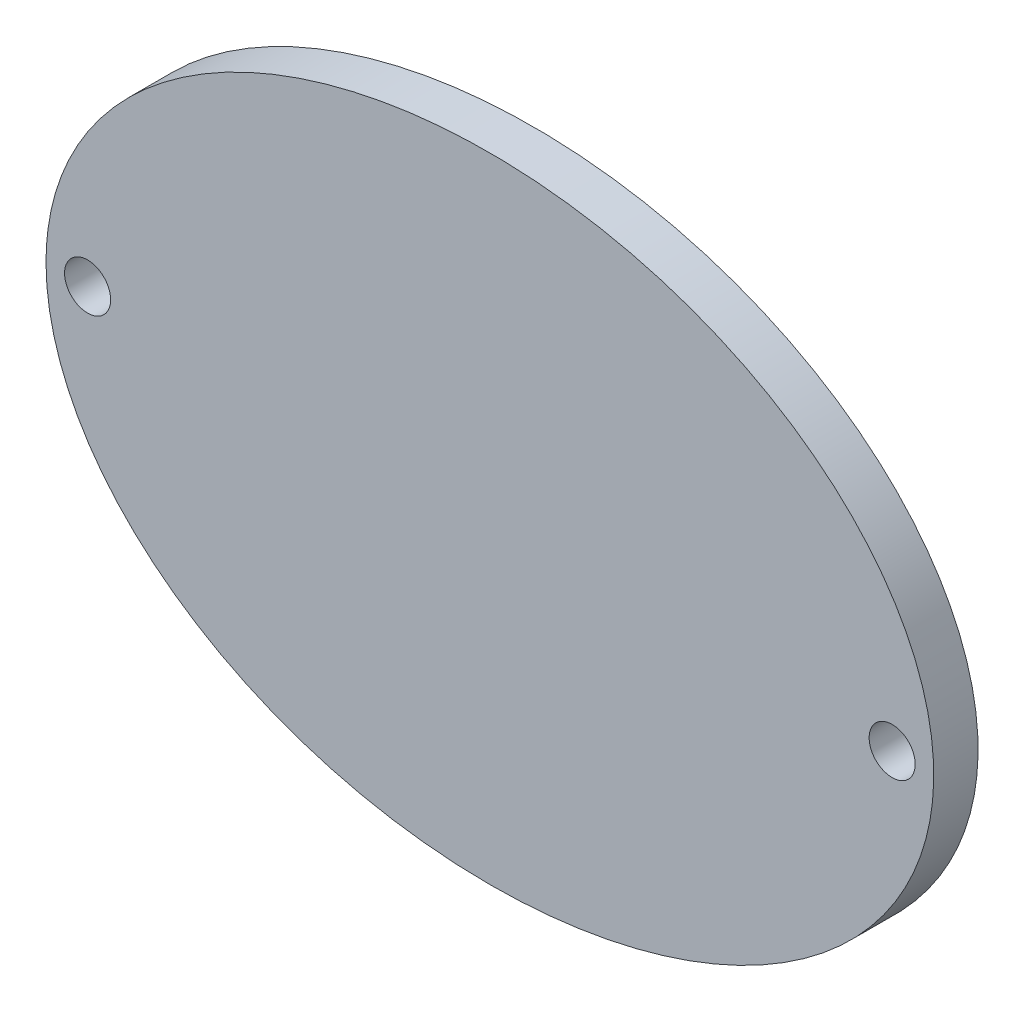
SolidWorks part; units mm, degrees
ref_plane "Plan de face" through (0, 0, 0) normal (0, 0, 1) x (1, 0, 0)
ref_plane "Plan de dessus" through (0, 0, 0) normal (0, 1, 0) x (1, 0, 0)
ref_plane "Plan de droite" through (0, 0, 0) normal (1, 0, 0) x (0, 0, -1)
sketch "Sketch1" plane through (0, 0, 0) normal (0, 0, 1) x (1, 0, 0)
  ellipse E0 centre (0, 0) end of major axis (-31.8, 0) minor radius 22.7
  point P1 (0, 0)
  dimension "D1" = 45.4
  dimension "D2" = 63.6
extrude "Boss-Extrude1" add sketch "Sketch1" along normal blind 3.175
sketch "Sketch2" plane through (0, 0, 0) normal (0, 0, -1) x (-1, 0, 0)
  line L0 (-28.82, 0) -> (28.82, 0) construction
  circle A0 centre (-28.82, 0) radius 1.65
  circle A1 centre (28.82, 0) radius 1.65
  point P4 (0, 0)
  dimension "D2" = 3.3
  dimension "D3" = 3.3
  dimension "D1" = 57.64
extrude "Cut-Extrude1" cut sketch "Sketch2" against normal blind 3.175
